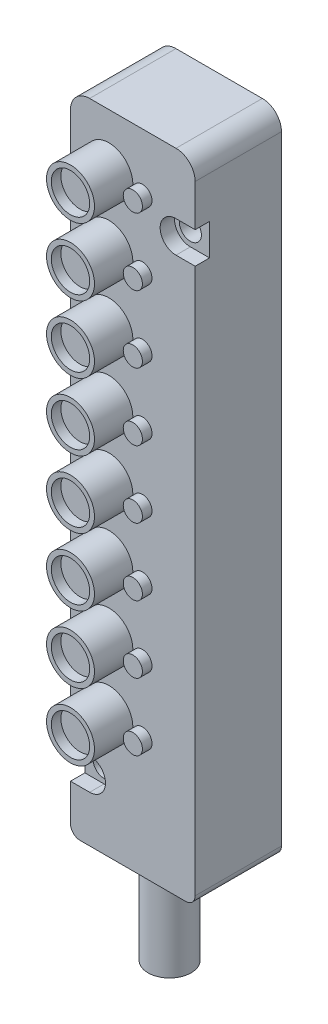
SolidWorks part; units mm, degrees
ref_plane "Plan de face" through (0, 0, 0) normal (0, 0, 1) x (1, 0, 0)
ref_plane "Plan de dessus" through (0, 0, 0) normal (0, 1, 0) x (1, 0, 0)
ref_plane "Plan de droite" through (0, 0, 0) normal (1, 0, 0) x (0, 0, -1)
sketch "Esquisse1" plane through (0, 0, 0) normal (0, 0, 1) x (1, 0, 0)
  line L1 (-11, -67.5) -> (11, -67.5)
  line L2 (-13, -65.5) -> (-13, 63.5)
  line L3 (-9, 67.5) -> (9, 67.5)
  line L4 (13, -65.5) -> (13, 63.5)
  line L5 (-13, -67.5) -> (13, 67.5) construction
  line L6 (-13, 67.5) -> (13, -67.5) construction
  arc A0 (-13, 63.5) -> (-9, 67.5) centre (-9, 63.5) cw
  arc A1 (13, 63.5) -> (9, 67.5) centre (9, 63.5) ccw
  arc A2 (11, -67.5) -> (13, -65.5) centre (11, -65.5) ccw
  arc A3 (-11, -67.5) -> (-13, -65.5) centre (-11, -65.5) cw
  point P0 (0, 0)
  dimension "D3" = 4
  dimension "D4" = 2
  dimension "D1" = 26
  dimension "D2" = 135
extrude "Boss.-Extru.1" add sketch "Esquisse1" along normal blind 18
sketch "Esquisse2" plane through (0, 0, 18) normal (0, 0, 1) x (1, 0, 0)
  line L0 (0, 67.5) -> (0, -75.287) construction
  line L1 (9, 67.5) -> (-9, 67.5) construction
  line L2 (9, 67.5) -> (9, 43.6854) construction
  line L3 (-11, -67.5) -> (11, -67.5) construction
  line L4 (9, 51.5) -> (19.3706, 51.5) construction
  line L5 (9, 54.8) -> (19.3706, 54.8)
  line L6 (9, 48.2) -> (19.3706, 48.2)
  circle A0 centre (9, 51.5) radius 2.3
  arc A1 (9, 54.8) -> (9, 48.2) centre (9, 51.5) ccw
  arc A2 (19.3706, 48.2) -> (19.3706, 54.8) centre (19.3706, 51.5) ccw
  point P13 (14.1853, 51.5)
  dimension "D1" = 4.6
  dimension "D3" = 3.3
  dimension "D2" = 119
extrude "Enlèv. mat.-Extru.1" cut sketch "Esquisse2" against normal blind 3
sketch "Esquisse4" plane through (0, 0, 18) normal (0, 0, 1) x (1, 0, 0)
  circle A2 centre (9, 51.5) radius 2.3
  circle A3 centre (9, 51.5) radius 2.3
  dimension "D1" = 0
extrude "Enlèv. mat.-Extru.2" cut sketch "Esquisse4" against normal through all
sketch "Esquisse5" plane through (0, 0, 18) normal (0, 0, 1) x (1, 0, 0)
  line L0 (-9, 67.5) -> (-9, -77.4732) construction
  line L1 (-11, -67.5) -> (11, -67.5) construction
  line L2 (-9, -54.5) -> (-17.2991, -54.5) construction
  line L3 (-9, -57.8) -> (-17.2991, -57.8)
  line L4 (-9, -51.2) -> (-17.2991, -51.2)
  circle A0 centre (-9, -54.5) radius 2.3
  arc A1 (-9, -57.8) -> (-9, -51.2) centre (-9, -54.5) ccw
  arc A2 (-17.2991, -51.2) -> (-17.2991, -57.8) centre (-17.2991, -54.5) ccw
  point P10 (-13.1496, -54.5)
  dimension "D1" = 4.6
  dimension "D3" = 3.3
  dimension "D2" = 13
extrude "Enlèv. mat.-Extru.3" cut sketch "Esquisse5" against normal blind 3
sketch "Esquisse6" plane through (0, 0, 18) normal (0, 0, 1) x (1, 0, 0)
  circle A2 centre (-9, -54.5) radius 2.3
  circle A3 centre (-9, -54.5) radius 2.3
  dimension "D1" = 0
extrude "Enlèv. mat.-Extru.4" cut sketch "Esquisse6" against normal through all
sketch "Esquisse7" plane through (0, 0, 18) normal (0, 0, 1) x (1, 0, 0)
  line L0 (0, 67.5) -> (0, -89.5209) construction
  line L1 (9, 67.5) -> (-9, 67.5) construction
  line L2 (-11, -67.5) -> (11, -67.5) construction
  circle A0 centre (-5, -41.5) radius 5
  circle A1 centre (-5, -41.5) radius 4
  dimension "D3" = 10
  dimension "D4" = 8
  dimension "D1" = 26
  dimension "D2" = 5
extrude "Boss.-Extru.2" add sketch "Esquisse7" along normal blind 6 contours A1 region at (-5, -41.5, 18)
extrude "Boss.-Extru.3" add sketch "Esquisse7<5>" along normal blind 8
sketch "Esquisse7<5>" plane through (0, 0, 18) normal (0, 0, 1) x (1, 0, 0) same geometry as "Esquisse7"
pattern_linear "Répétition linéaire1" count 8 spacing 14 along (0, 1, 0) of "Boss.-Extru.2", "Boss.-Extru.3"
sketch "Esquisse8" plane through (0, 0, 18) normal (0, 0, 1) x (1, 0, 0)
  line L0 (0, 67.5) -> (0, -67.5) construction
  line L1 (9, 67.5) -> (-9, 67.5) construction
  line L2 (-11, -67.5) -> (11, -67.5) construction
  circle A0 centre (2, -42.5) radius 2
  dimension "D1" = 4
  dimension "D2" = 2
  dimension "D3" = 25
extrude "Boss.-Extru.4" add sketch "Esquisse8" along normal blind 2
pattern_linear "Répétition linéaire2" count 8 spacing 14 along (0, 1, 0) of "Boss.-Extru.4"
sketch "Esquisse9" plane through (0, -67.5, 0) normal (0, -1, 0) x (1, 0, 0)
  circle A0 centre (0, 10.3367) radius 4.5
  dimension "D1" = 9
extrude "Boss.-Extru.5" add sketch "Esquisse9" along normal blind 20
